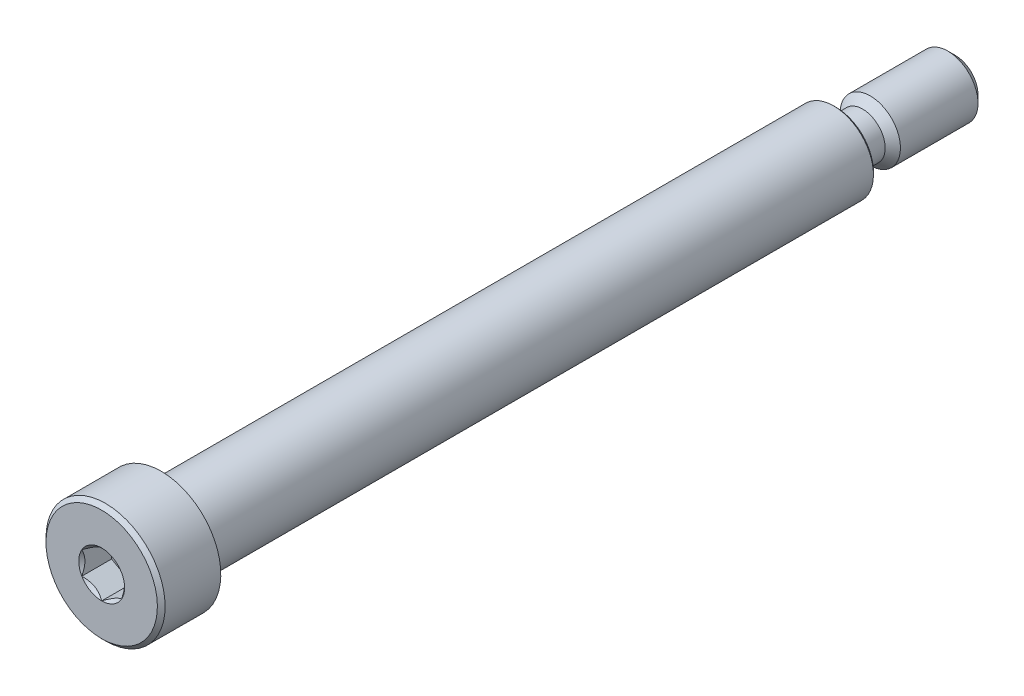
SolidWorks part; units mm, degrees
material "Cast Alloy Steel"
ref_plane "Front" through (0, 0, 0) normal (0, 0, 1) x (1, 0, 0)
ref_plane "Top" through (0, 0, 0) normal (0, 1, 0) x (1, 0, 0)
ref_plane "Right" through (0, 0, 0) normal (1, 0, 0) x (0, 0, -1)
sketch "Sketch1" plane through (0, 0, 0) normal (1, 0, 0) x (0, 0, -1)
  line L0 (0, 4.7625) -> (4.7625, 4.7625)
  line L1 (4.7625, 4.7625) -> (4.7625, 3.175)
  line L2 (4.7625, 3.175) -> (58.7375, 3.175)
  line L3 (58.7375, 3.175) -> (58.7375, 2.413)
  line L4 (58.7375, 2.413) -> (68.2625, 2.413)
  line L5 (68.2625, 2.413) -> (68.2625, 0)
  line L6 (68.2625, 0) -> (0, 0)
  line L7 (0, 0) -> (0, 4.7625)
  line L8 (0, 4.7625) -> (0, -4.7625) construction
  line L9 (68.2625, 2.413) -> (68.2625, -2.413) construction
  line L10 (58.7375, 3.175) -> (58.7375, -3.175) construction
  line L11 (68.2625, -2.413) -> (66.5847, -2.413) construction
  line L12 (31.75, 0) -> (31.75, 3.175) construction
  point P8 (66.675, -2.413)
  point P12 (58.7375, 0)
  point P17 (10.16, 3.175)
  point P18 (31.75, 0)
  point P19 (31.75, 3.175)
  point P20 (53.34, 3.175)
  point P21 (53.34, -3.175)
  point P22 (10.16, -3.175)
  dimension "Head Dia" = 9.525
  dimension "Head Ht" = 4.7625
  dimension "Thread Lg" = 9.525
  dimension "Thread Dia" = 4.826
  dimension "Shoulder Dia" = 6.35
  dimension "Shoulder Lg" = 53.975
  dimension "D1" = 1.5875
  dimension "D2" = 1.6778
  dimension "D3" = 26.9875
  dimension "D4" = 5.3975
revolve "Revolve1" add sketch "Sketch1" angle 360 mid plane about L6
ref_plane "Plane1" through (0, 0, -68.2625) normal (0, 0, 1) x (1, 0, 0)
sketch "Sketch3" [suppressed] plane through (0, 0, -68.2625) normal (0, 0, 1) x (1, 0, 0)
  circle A0 centre (0, 0) radius 2.413
sketch "Sketch5" plane through (0, 0, 0) normal (1, 0, 0) x (0, 0, -1)
  line L0 (58.7375, 3.175) -> (62.2173, 3.175)
  line L1 (62.2173, 3.175) -> (60.8457, 1.8034)
  line L2 (60.8457, 1.8034) -> (59.3471, 1.8034)
  line L3 (58.7375, 3.175) -> (58.7375, 2.413)
  line L5 (58.7375, 2.413) -> (68.2625, 2.413) construction
  line L6 (68.2625, 0) -> (60.8457, 0) construction
  line L7 (64.5541, 0) -> (64.5541, -2.413) construction
  arc A0 (58.7375, 2.413) -> (59.3471, 1.8034) centre (59.3471, 2.413) ccw
  dimension "D1" = 45
  dimension "CADB" = 2.1082
  dimension "CADA" = 3.6068
revolve "Cut-Revolve1" cut sketch "Sketch5" angle 360 mid plane about L6
chamfer "Chamfer1" distance 0.6032 angle 45 1 edges at (0, 2.413, -68.2625)
chamfer "Chamfer2" distance 0.3096 angle 45 1 edges at (0, 4.7625, 0)
chamfer "Chamfer3" distance 0.2032 angle 45 1 edges at (0, 3.175, -58.7375)
sketch "Sketch10" plane through (0, 0, 0) normal (1, 0, 0) x (0, 0, -1)
  line L0 (0.3096, 0) -> (4.4529, 0) construction
  line L1 (0.3096, -4.7625) -> (0.3096, 4.7625) construction
  line L3 (0.3096, 0) -> (0, 0) construction
  line L4 (4.4529, 0) -> (4.7625, 0) construction
  line L5 (4.7625, -4.7625) -> (4.7625, 4.7625) construction
  point P6 (2.3812, 0)
  dimension "D1" = 4.1434
ref_plane "Plane2" through (0, 0, -2.3812) normal (0, 0, 1) x (1, 0, 0)
sketch "Sketch11" plane through (0, 0, -2.3812) normal (0, 0, 1) x (1, 0, 0)
  line L0 (0, 4.5148) -> (0, 4.7625) construction
  line L1 (0, 4.5148) -> (0.143, 4.7625)
  line L2 (0, 4.5148) -> (-0.143, 4.7625)
  line L3 (-0.143, 4.7625) -> (0.143, 4.7625)
  line L4 (0, 0) -> (-0.143, 4.7625) construction
  line L5 (0.143, 4.7625) -> (0, 0) construction
  circle A1 centre (0, 0) radius 4.7625 construction
  circle A2 centre (0, 0) radius 4.5148 construction
  circle A3 centre (0, 0) radius 4.4529 construction
  point P3 (0, 0.0018)
  point P8 (2.3908, 0.7309)
  dimension "D1" = 0.2476
  dimension "D2" = 3.439
extrude "Cut-Extrude5" [suppressed] cut sketch "Sketch11" against normal mid plane 3.9362
pattern_circular "CirPattern1" [suppressed] count 99 over 360 of bodies 119
sketch "Sketch8" plane through (0, 0, 0) normal (0, 0, 1) x (1, 0, 0)
  line L1 (1.5875, 0.9165) -> (0, 1.8331)
  line L2 (0, 1.8331) -> (-1.5875, 0.9165)
  line L3 (-1.5875, 0.9165) -> (-1.5875, -0.9165)
  line L4 (-1.5875, -0.9165) -> (0, -1.8331)
  line L5 (0, -1.8331) -> (1.5875, -0.9165)
  line L6 (1.5875, -0.9165) -> (1.5875, 0.9165)
  circle A0 centre (0, 0) radius 1.5875 construction
  dimension "Hex" = 3.175
extrude "Cut-Extrude2" cut sketch "Sketch8" against normal blind 2.3813
sketch "Sketch9" plane through (0, 0, 0) normal (0, 0, 1) x (1, 0, 0)
  circle A0 centre (0, 0) radius 1.8331
extrude "Cut-Extrude4" cut sketch "Sketch9" against normal blind 2.3813 draft 45
sketch "Front Sketch" plane through (0, 0, 0) normal (0, 0, 1) x (1, 0, 0)
  line L0 (1.5875, -0.9165) -> (1.5875, 0.9165) construction
  line L1 (-1.5875, 0.9165) -> (-1.5875, -0.9165) construction
  circle A0 centre (0, 0) radius 4.7625 construction
  point P4 (-1.5875, 0)
  point P5 (1.5875, 0)
  point P6 (4.7625, 0)
  point P9 (-4.7625, 0)
ref_plane "Contact Plane 1" [suppressed] through (0, 0, -4.7625) normal (0, 0, -1) x (-1, 0, 0)
ref_axis "Center Axis 1" [suppressed] through (0, 0, -68.2625) along (0, 0, 1)
curve "Helix/Spiral1" [suppressed] pitch 1.0583 height 10.5833 turns 10
sketch "Sketch4" [suppressed] plane through (0, 0, 0) normal (1, 0, 0) x (0, 0, -1)
  line L0 (68.1964, 2.5276) -> (69.2547, 2.5276) construction
  line L1 (69.2547, 2.5276) -> (68.7255, 1.611) construction
  line L3 (68.7255, 1.611) -> (68.1964, 2.5276) construction
  line L4 (68.2294, 2.4703) -> (69.2216, 2.4703) construction
  line L5 (68.2625, 2.413) -> (69.1885, 2.413) construction
  line L6 (68.6594, 1.7256) -> (68.7917, 1.7256) construction
  line L7 (68.7255, 1.7256) -> (68.7255, 1.611) construction
  line L8 (68.7255, 2.5276) -> (68.7255, 2.413) construction
  line L9 (68.2294, 2.4703) -> (69.2216, 2.4703)
  line L10 (69.2216, 2.4703) -> (68.7917, 1.7256)
  line L11 (68.7917, 1.7256) -> (68.6594, 1.7256)
  line L12 (68.6594, 1.7256) -> (68.2294, 2.4703)
  point P14 (68.7255, 2.4703)
  point P15 (68.7255, 2.5276)
  dimension "D1" = 1.0583
  dimension "D2" = 0.1323
sweep "Cut-Sweep1" [suppressed] cut profiles "Sketch4" path "Helix/Spiral1"
sketch "Sketch12" [suppressed] plane through (0, 0, 0) normal (1, 0, 0) x (0, 0, -1)
  line L1 (58.7375, 2.9718) -> (58.5343, 3.175)
  line L2 (58.5343, 3.175) -> (4.7625, 3.175)
  line L3 (4.7625, 3.175) -> (4.7625, 0)
  line L4 (4.7625, -4.7625) -> (4.7625, 4.7625) construction
  line L5 (4.7625, 0) -> (58.7375, 0)
  line L6 (58.7375, 2.9718) -> (58.7375, 2.413)
  line L7 (60.8457, 1.8034) -> (59.3471, 1.8034) construction
  line L8 (60.8457, 1.8034) -> (59.3471, 1.8034)
  line L9 (60.8457, 1.8034) -> (60.8457, 0)
  line L10 (60.8457, 0) -> (58.7375, 0)
  arc A0 (58.7375, 2.413) -> (59.3471, 1.8034) centre (59.3471, 2.413) ccw construction
  arc A1 (58.7375, 2.413) -> (59.3471, 1.8034) centre (59.3471, 2.413) ccw
revolve "Revolve2" [suppressed] add sketch "Sketch12" angle 360 about L5
equation "\"D3@Helix/Spiral1\" = \"Thread Lg@Sketch1\" + \"D4@Helix/Spiral1\""
equation "\"D1@Chamfer1\" = \"Thread Dia@Sketch1\" * .125"
equation "\"D1@Cut-Extrude2\"= \"Head Ht@Sketch1\" * .5"
equation "\"D1@Cut-Extrude4\" = \"D1@Cut-Extrude2\""
equation "\"D1@Chamfer2\" = \"Head Dia@Sketch1\" * .0325"
equation "\"D1@Sketch1\"=\"D4@Helix/Spiral1\"*1.5"
equation "\"D1@Sketch11\"=\"D1@Chamfer2\"*.8"
equation "\"D1@Cut-Extrude5\"=\"D1@Sketch10\"*.95"
equation "\"D1@CirPattern1\"=(360/\"D2@Sketch11\")-6"
equation "\"D3@Sketch1\"=\"Shoulder Lg@Sketch1\"/2"
equation "\"D4@Sketch1\"=\"D3@Sketch1\"*.2"
equation "\"D1@Sketch4\"=\"D4@Helix/Spiral1\""
equation "\"D2@Sketch4\"=\"D1@Sketch4\"/8"
